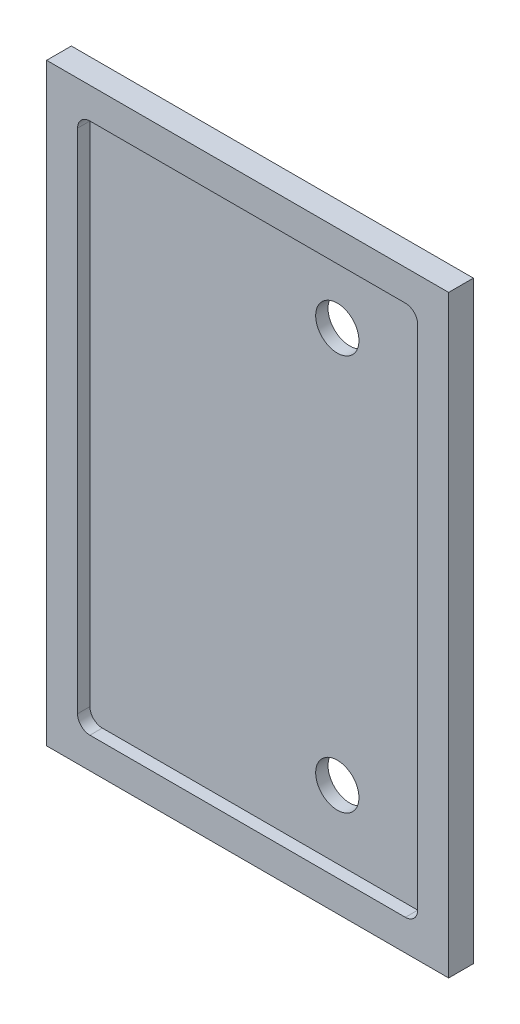
SolidWorks part; units mm, degrees
ref_plane "Front Plane" through (0, 0, 0) normal (0, 0, 1) x (1, 0, 0)
ref_plane "Top Plane" through (0, 0, 0) normal (0, 1, 0) x (1, 0, 0)
ref_plane "Right Plane" through (0, 0, 0) normal (1, 0, 0) x (0, 0, -1)
sketch "Sketch1" plane through (0, 0, 0) normal (0, 0, 1) x (1, 0, 0)
  line L1 (103.1875, -152.4) -> (-103.1875, -152.4)
  line L2 (103.1875, -152.4) -> (103.1875, 152.4)
  line L3 (103.1875, 152.4) -> (-103.1875, 152.4)
  line L4 (-103.1875, -152.4) -> (-103.1875, 152.4)
  line L5 (103.1875, -152.4) -> (-103.1875, 152.4) construction
  line L6 (103.1875, 152.4) -> (-103.1875, -152.4) construction
  point P0 (0, 0)
  dimension "D1" = 304.8
  dimension "D2" = 206.375
extrude "Boss-Extrude1" add sketch "Sketch1" along normal blind 12.7
sketch "Sketch2" plane through (0, 0, 12.7) normal (0, 0, 1) x (1, 0, 0)
  line L0 (-103.1875, 152.4) -> (-103.1875, -152.4) construction
  line L1 (80.9625, -136.525) -> (-80.9625, -136.525)
  line L2 (87.3125, -130.175) -> (87.3125, 130.175)
  line L3 (80.9625, 136.525) -> (-80.9625, 136.525)
  line L4 (-87.3125, -130.175) -> (-87.3125, 130.175)
  line L5 (87.3125, -136.525) -> (-87.3125, 136.525) construction
  line L6 (87.3125, 136.525) -> (-87.3125, -136.525) construction
  line L7 (103.1875, 152.4) -> (-103.1875, 152.4) construction
  arc A0 (-80.9625, -136.525) -> (-87.3125, -130.175) centre (-80.9625, -130.175) cw
  arc A1 (80.9625, -136.525) -> (87.3125, -130.175) centre (80.9625, -130.175) ccw
  arc A2 (87.3125, 130.175) -> (80.9625, 136.525) centre (80.9625, 130.175) ccw
  arc A3 (-80.9625, 136.525) -> (-87.3125, 130.175) centre (-80.9625, 130.175) ccw
  point P0 (0, 0)
  dimension "D3" = 6.35
  dimension "D1" = 15.875
  dimension "D2" = 15.875
extrude "Cut-Extrude1" cut sketch "Sketch2" against normal blind 6.35
sketch "Sketch4" plane through (0, 0, 0) normal (0, 0, -1) x (-1, 0, 0)
  line L0 (103.1875, -152.4) -> (-103.1875, -152.4) construction
  line L1 (-103.1875, -152.4) -> (-103.1875, 152.4) construction
  line L2 (0, 0) -> (-117.2439, 0) construction
  circle A0 centre (-39.6875, -101.6) radius 11.1125
  circle A1 centre (-39.6875, 101.6) radius 11.1125
  dimension "D1" = 22.225
  dimension "D2" = 50.8
  dimension "D3" = 63.5
  dimension "D4" = 0
extrude "Cut-Extrude3" cut sketch "Sketch4" against normal through all
